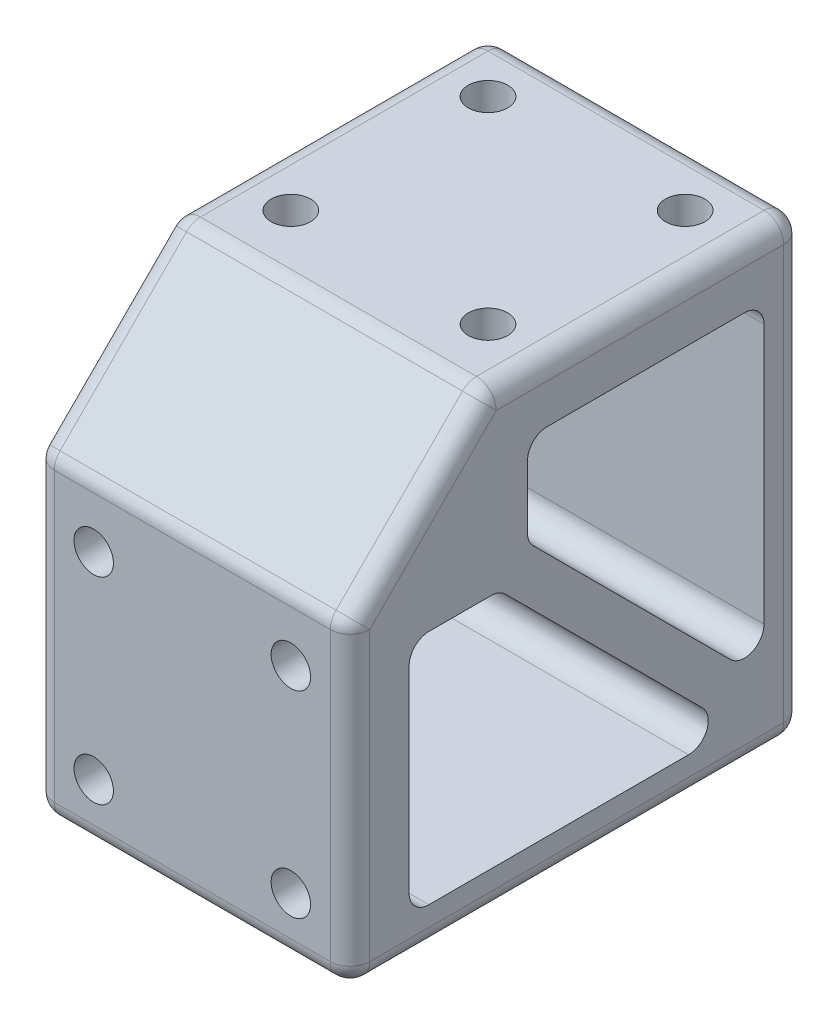
SolidWorks part; units mm, degrees
ref_plane "Front Plane" through (0, 0, 0) normal (0, 0, 1) x (1, 0, 0)
ref_plane "Top Plane" through (0, 0, 0) normal (0, 1, 0) x (1, 0, 0)
ref_plane "Right Plane" through (0, 0, 0) normal (1, 0, 0) x (0, 0, -1)
sketch "Sketch1" plane through (0, 0, 1008.2477) normal (0, 0, -1) x (-1, 0, 0)
  line L1 (-1530.8027, 8) -> (-1530.8027, 16)
  line L2 (-1530.8027, 15) -> (-1530.8027, 1) construction
  line L3 (-1530.8027, 16) -> (-1514.8027, 16)
  line L4 (-1514.8027, 16) -> (-1514.8027, 0)
  line L5 (-1514.8027, 0) -> (-1530.8027, 0)
  line L6 (-1530.8027, 0) -> (-1530.8027, 8)
  circle A0 centre (-1527.8027, 13) radius 1
  circle A1 centre (-1517.8027, 13) radius 1
  circle A2 centre (-1517.8027, 3) radius 1
  circle A3 centre (-1527.8027, 3) radius 1
extrude "Boss-Extrude1" add sketch "Sketch1" along normal blind 3
sketch "Sketch2" plane through (0, 0, 1005.2477) normal (0, 0, -1) x (-1, 0, 0)
  line L10 (-1516.8027, 14) -> (-1528.8027, 14)
  line L11 (-1528.8027, 14) -> (-1528.8027, 2)
  line L12 (-1528.8027, 2) -> (-1516.8027, 2)
  line L13 (-1516.8027, 2) -> (-1516.8027, 14)
  line L14 (-1514.8027, 0) -> (-1514.8027, 16)
  line L15 (-1530.8027, 0) -> (-1514.8027, 0)
  line L16 (-1530.8027, 16) -> (-1530.8027, 0)
  line L17 (-1514.8027, 16) -> (-1530.8027, 16)
  line L18 (-1514.8027, 0) -> (-1514.8027, 16)
  line L19 (-1530.8027, 0) -> (-1514.8027, 0)
  line L20 (-1530.8027, 16) -> (-1530.8027, 0)
  line L21 (-1514.8027, 16) -> (-1530.8027, 16)
  dimension "D1" = 0
  dimension "D2" = 2
sketch "Sketch3" plane through (1530.8027, 0, 0) normal (1, 0, 0) x (0, 0, -1)
  line L0 (-1005.2477, 16) -> (-1005.2477, 14)
  line L1 (-1005.2477, 0) -> (-985.2477, 0)
  line L2 (-985.2477, 0) -> (-985.2477, 23)
  line L3 (-985.2477, 23) -> (-1001.2477, 23)
  line L7 (-1001.2477, 20) -> (-985.2477, 20) construction
  line L8 (-1005.2477, 2) -> (-1005.2477, 0)
  line L9 (-1000.6619, 14) -> (-988.6619, 2)
  line L10 (-999.2477, 15.4142) -> (-987.2477, 3.4142)
  line L11 (-999.2477, 20) -> (-999.2477, 15.4142)
  line L12 (-1000.6619, 14) -> (-1005.2477, 14)
  line L13 (-1005.2477, 2) -> (-988.6619, 2)
  line L14 (-999.2477, 20) -> (-987.2477, 20)
  line L15 (-1001.2477, 23) -> (-1008.2477, 16)
  line L16 (-1008.2477, 16) -> (-1005.2477, 16)
  line L17 (-1005.2477, 2) -> (-985.2477, 2) construction
  line L18 (-987.2477, 3.4142) -> (-987.2477, 20)
  dimension "D2" = 2
extrude "Boss-Extrude3" add sketch "Sketch3" against normal blind 16
sketch "Sketch4" plane through (0, 23, 0) normal (0, 1, 0) x (1, 0, 0)
  circle A0 centre (1527.8027, -988.2477) radius 1
  circle A1 centre (1517.8027, -988.2477) radius 1
  circle A2 centre (1517.8027, -998.2477) radius 1
  circle A3 centre (1527.8027, -998.2477) radius 1
extrude "Cut-Extrude1" cut sketch "Sketch4" against normal blind 5
fillet "Fillet1" radius 1 31 edges at (1530.8027, 0, 996.7477) (1514.8027, 0, 996.7477) (1522.8027, 0, 1008.2477) (1522.8027, 23, 985.2477) (1514.8027, 11.5, 985.2477) (1522.8027, 0, 985.2477) (1530.8027, 11.5, 985.2477) (1522.8027, 16, 1008.2477) (1530.8027, 8, 1008.2477) (1514.8027, 8, 1008.2477) (1514.8027, 19.5, 1004.7477) (1530.8027, 23, 993.2477) (1530.8027, 19.5, 1004.7477) (1529.3027, 2, 1005.2477) (1516.3027, 2, 1005.2477) (1522.8027, 2, 1005.2477) (1516.3027, 14, 1005.2477) (1529.3027, 14, 1005.2477) (1516.3027, 20, 987.2477) (1522.8027, 20, 987.2477) (1516.3027, 20, 999.2477) (1522.8027, 20, 999.2477) (1529.3027, 20, 999.2477) (1522.8027, 14, 1005.2477) (1529.3027, 20, 987.2477) (1522.8027, 2, 988.6619) (1522.8027, 14, 1000.6619) (1522.8027, 3.4142, 987.2477) (1522.8027, 15.4142, 999.2477) (1522.8027, 23, 1001.2477) (1514.8027, 23, 993.2477)
